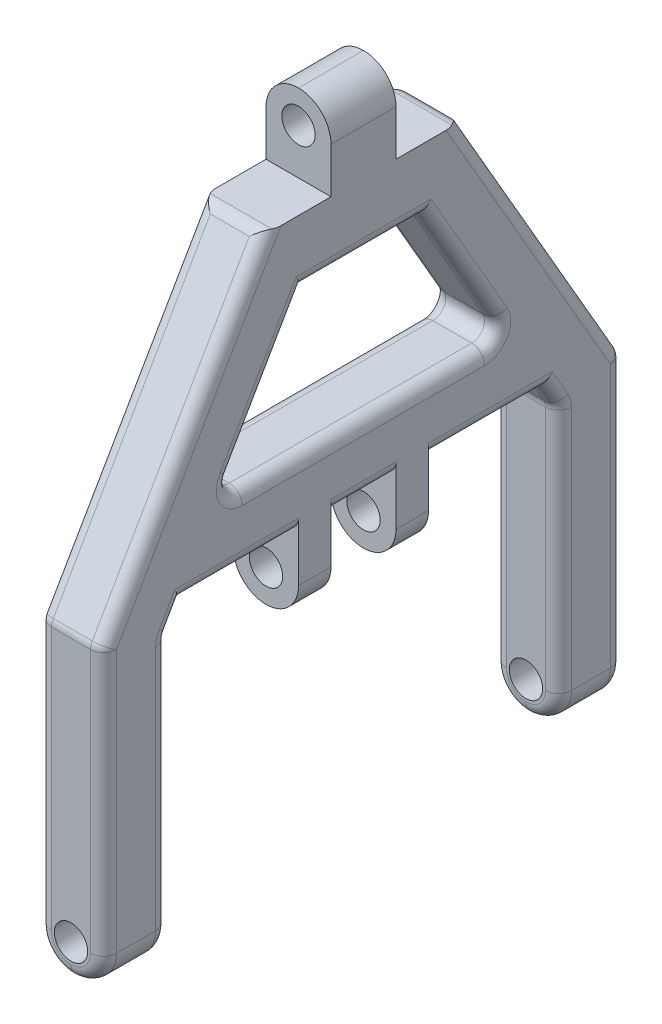
SolidWorks part; units mm, degrees
ref_plane "Front Plane" through (0, 0, 0) normal (0, 0, 1) x (1, 0, 0)
ref_plane "Top Plane" through (0, 0, 0) normal (0, 1, 0) x (1, 0, 0)
ref_plane "Right Plane" through (0, 0, 0) normal (1, 0, 0) x (0, 0, -1)
sketch "Sketch2" plane through (0, 0, 0) normal (1, 0, 0) x (0, 0, -1)
  line L0 (-25.4, 3.175) -> (-25.4, 26.035)
  line L1 (25.4, -3.175) -> (19.05, -3.175)
  line L2 (25.4, -3.175) -> (25.4, 3.175)
  line L4 (-25.4, -3.175) -> (-25.4, 3.175)
  line L5 (25.4, -3.175) -> (-25.4, 3.175) construction
  line L6 (25.4, 3.175) -> (-25.4, -3.175) construction
  line L7 (-25.4, 26.035) -> (-9.525, 53.5313)
  line L8 (-9.525, 53.5313) -> (0, 53.5313)
  line L9 (-19.05, 3.175) -> (-19.05, 9.525)
  line L10 (-19.05, 24.3335) -> (-17.7081, 26.6578)
  line L11 (-5.8588, 47.1813) -> (0, 47.1813)
  line L12 (-14.0419, 33.0078) -> (14.0419, 33.0078)
  line L13 (0, 55) -> (0, -55) construction
  line L14 (17.7081, 26.6578) -> (-17.7081, 26.6578)
  line L15 (-14.0419, 33.0078) -> (-5.8588, 47.1813)
  line L16 (-19.05, 24.3335) -> (-5.8588, 47.1813) construction
  line L17 (25.4, 3.175) -> (25.4, 26.035)
  line L19 (19.05, 24.3335) -> (17.7081, 26.6578)
  line L20 (14.0419, 33.0078) -> (5.8588, 47.1813)
  line L21 (25.4, 26.035) -> (9.525, 53.5313)
  line L22 (9.525, 53.5313) -> (0, 53.5313)
  line L23 (5.8588, 47.1813) -> (0, 47.1813)
  line L24 (-19.05, 3.175) -> (-19.05, -3.175)
  line L25 (19.05, 3.175) -> (19.05, -3.175)
  line L26 (-19.05, -3.175) -> (-25.4, -3.175)
  line L32 (-19.05, 3.175) -> (-19.05, 24.3335) construction
  line L34 (-19.05, 24.3335) -> (-19.05, 9.525)
  line L35 (19.05, 24.3335) -> (19.05, 3.175)
  point P0 (0, 0)
  point P26 (0, 26.6578)
  point P27 (0, 33.0078)
  dimension "D1" = 50.8
  dimension "D2" = 22.86
  dimension "D3" = 31.75
  dimension "D4" = 6.35
  dimension "D5" = 150
  dimension "D7" = 6.35
  dimension "D8" = 14.1735
  dimension "D9" = 6.35
  dimension "D6" = 6.35
extrude "Boss-Extrude1" add sketch "Sketch2" along normal mid plane 6.35 contours L21 L22 L8 L7 L0 L9 L10 L14 L19 L4 L1 L2 L17 L23 L20 L12 L15 L11 region at (0, 28.0616, 0)
sketch "Sketch4" plane through (0, 26.6578, 0) normal (0, -1, 0) x (1, 0, 0)
  line L0 (3.175, -17.7081) -> (3.175, 17.7081) construction
  line L1 (-3.175, -6.35) -> (3.175, -6.35)
  line L2 (-3.175, -6.35) -> (-3.175, 6.35) construction
  line L3 (-3.175, 6.35) -> (3.175, 6.35)
  line L4 (3.175, -6.35) -> (3.175, 6.35) construction
  line L5 (-3.175, -6.35) -> (3.175, 6.35) construction
  line L6 (-3.175, 6.35) -> (3.175, -6.35) construction
  line L7 (3.175, 3.175) -> (3.175, 6.35)
  line L8 (-3.175, -3.175) -> (3.175, -3.175)
  line L9 (-3.175, -3.175) -> (-3.175, 3.175) construction
  line L10 (-3.175, 3.175) -> (3.175, 3.175)
  line L11 (3.175, -3.175) -> (3.175, 3.175) construction
  line L12 (-3.175, -3.175) -> (3.175, 3.175) construction
  line L13 (-3.175, 3.175) -> (3.175, -3.175) construction
  line L14 (-3.175, 3.175) -> (-3.175, 6.35)
  line L15 (-3.175, -3.175) -> (-3.175, -6.35)
  line L16 (3.175, -6.35) -> (3.175, -3.175)
  point P0 (0, 0)
  point P8 (0, 0)
  dimension "D1" = 12.7
  dimension "D2" = 6.35
extrude "Boss-Extrude3" add sketch "Sketch4" along normal blind 7.62
fillet "Fillet2" radius 1.27 42 edges at (3.175, 26.6578, 0) (3.175, 26.6578, 12.029) (3.175, 25.4957, 18.379) (3.175, 10.5793, 19.05) (3.175, 25.4957, -18.379) (3.175, 26.6578, -12.029) (3.175, 47.1813, 0) (3.175, 40.0945, 9.9504) (3.175, 33.0078, 0) (3.175, 40.0945, -9.9504) (3.175, 39.7832, -17.4625) (3.175, 11.43, -25.4) (3.175, 11.43, 25.4) (3.175, 39.7832, 17.4625) (-3.175, 26.6578, -12.029) (-3.175, 25.4957, -18.379) (-3.175, 10.5793, 19.05) (-3.175, 25.4957, 18.379) (-3.175, 26.6578, 12.029) (-3.175, 26.6578, 0) (-3.175, 40.0945, -9.9504) (-3.175, 33.0078, 0) (-3.175, 40.0945, 9.9504) (-3.175, 47.1813, 0) (-3.175, 11.43, -25.4) (-3.175, 39.7832, -17.4625) (-3.175, 39.7832, 17.4625) (-3.175, 11.43, 25.4) (0, 53.5313, 9.525) (0, 53.5313, -9.525) (0, -3.175, -25.4) (0, 33.0078, -14.0419) (0, 33.0078, 14.0419) (0, 24.3335, 19.05) (0, 26.035, -25.4) (0, 26.035, 25.4) (0, -3.175, -19.05) (0, -3.175, 19.05) (0, -3.175, 25.4) (0, 24.3335, -19.05) (3.175, 10.5793, -19.05) (-3.175, 10.5793, -19.05)
sketch "Sketch8" plane through (0, 53.5313, 0) normal (0, 1, 0) x (1, 0, 0)
  line L0 (-3.175, 8.0585) -> (-3.175, -8.0585) construction
  line L1 (3.175, -3.175) -> (-3.175, -3.175)
  line L2 (3.175, -3.175) -> (3.175, 3.175)
  line L3 (3.175, 3.175) -> (-3.175, 3.175)
  line L4 (-3.175, -3.175) -> (-3.175, 3.175)
  line L5 (3.175, -3.175) -> (-3.175, 3.175) construction
  line L6 (3.175, 3.175) -> (-3.175, -3.175) construction
  point P0 (0, 0)
extrude "Boss-Extrude5" add sketch "Sketch8" along normal blind 7.62
sketch "Sketch7" plane through (0, 0, -25.4) normal (0, 0, -1) x (-1, 0, 0)
  circle A0 centre (0, 0) radius 1.627
  dimension "D1" = 3.254
extrude "Cut-Extrude3" cut sketch "Sketch7" along direction (0, 0, 1) on the side against the normal blind 63.5
fillet "Fillet3" radius 3.175 18 edges at (-3.175, 19.0378, 4.7625) (-3.175, 19.0378, -4.7625) (3.175, 19.0378, -4.7625) (3.175, 19.0378, 4.7625) (-3.175, 61.1513, 0) (3.175, 61.1513, 0) (2.803, -2.803, 25.028) (2.803, -2.803, 19.422) (-2.803, -2.803, 25.028) (-2.803, -2.803, 19.422) (-3.175, -3.175, 22.225) (3.175, -3.175, 22.225) (2.803, -2.803, -25.028) (-2.803, -2.803, -25.028) (-3.175, -3.175, -22.225) (3.175, -3.175, -22.225) (2.803, -2.803, -19.422) (-2.803, -2.803, -19.422)
sketch "Sketch9" plane through (0, 0, 3.175) normal (0, 0, 1) x (1, 0, 0)
  circle A0 centre (0, 57.9763) radius 1.627
  dimension "D1" = 3.254
extrude "Cut-Extrude4" cut sketch "Sketch9" against normal up to surface (6.35 mm away) up to face at (0, 57.0963, -3.175)
sketch "Sketch10" plane through (0, 0, 6.35) normal (0, 0, 1) x (1, 0, 0)
  circle A0 centre (0, 22.2128) radius 1.627
  arc A1 (0, 19.0378) -> (3.175, 22.2128) centre (0, 22.2128) ccw construction
  dimension "D1" = 3.254
extrude "Cut-Extrude5" cut sketch "Sketch10" against normal up to surface (12.7 mm away) up to face at (0, 24.399, -6.35)
sketch "Sketch11" plane through (0, 0, 0) normal (0, 0, 1) x (1, 0, 0)
  line L0 (-3.175, 25.6947) -> (-3.175, 53.5313) construction
  line L1 (-3.175, 57.9763) -> (-3.175, 53.5313) construction
  line L2 (3.175, 57.9763) -> (3.175, 53.5313) construction
  line L3 (3.175, 53.5313) -> (3.175, 25.6947) construction
  line L4 (3.175, 25.6947) -> (3.175, 0) construction
  line L5 (-3.175, 0) -> (-3.175, 25.6947) construction
  line L6 (-3.175, 25.6947) -> (-3.175, 53.5313)
  line L7 (-3.175, 57.9763) -> (-3.175, 53.5313)
  line L8 (3.175, 57.9763) -> (3.175, 53.5313)
  line L9 (3.175, 53.5313) -> (3.175, 25.6947)
  line L10 (3.175, 25.6947) -> (3.175, 0)
  line L11 (-3.175, 0) -> (-3.175, 25.6947)
  circle A0 centre (0, 57.9763) radius 1.627 construction
  circle A1 centre (0, 0) radius 1.627 construction
  arc A2 (0, 61.1513) -> (-3.175, 57.9763) centre (0, 57.9763) ccw construction
  arc A3 (3.175, 57.9763) -> (0, 61.1513) centre (0, 57.9763) ccw construction
  arc A4 (0, -3.175) -> (3.175, 0) centre (0, 0) ccw construction
  arc A5 (-3.175, 0) -> (0, -3.175) centre (0, 0) ccw construction
  circle A6 centre (0, 57.9763) radius 1.627
  circle A7 centre (0, 0) radius 1.627
  arc A8 (0, 61.1513) -> (-3.175, 57.9763) centre (0, 57.9763) ccw
  arc A9 (3.175, 57.9763) -> (0, 61.1513) centre (0, 57.9763) ccw
  arc A10 (0, -3.175) -> (3.175, 0) centre (0, 0) ccw
  arc A11 (-3.175, 0) -> (0, -3.175) centre (0, 0) ccw
